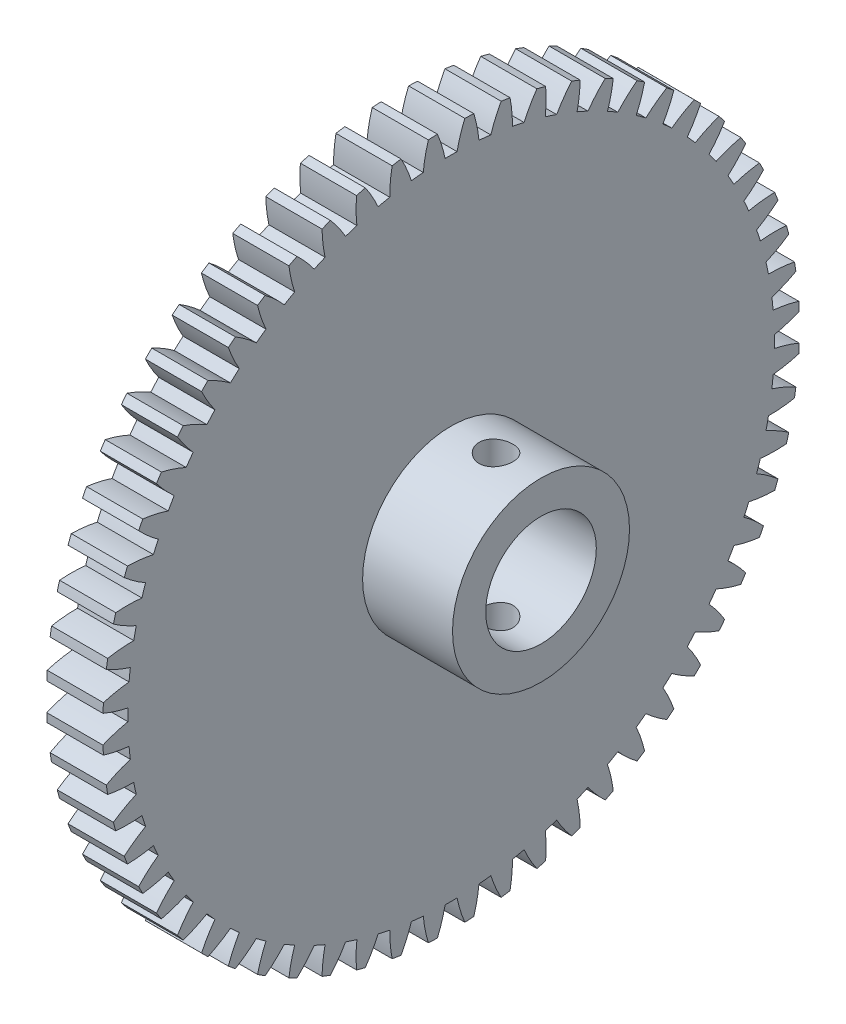
SolidWorks part; units mm, degrees
ref_plane "Plane1" through (0, 0, 0) normal (0, 0, 1) x (1, 0, 0)
ref_plane "Plane2" through (0, 0, 0) normal (0, 1, 0) x (1, 0, 0)
ref_plane "Plane3" through (0, 0, 0) normal (1, 0, 0) x (0, 0, -1)
sketch "HoldingSke" plane through (0, 0, 0) normal (0, 1, 0) x (1, 0, 0)
  line L0 (0, 0) -> (254, -439.9409)
  line L1 (-15, 0) -> (100, 0) construction
  line L2 (0, 0) -> (-2.1039, 2.3779)
  line L3 (0, 0) -> (-11.863, 4.5341)
  line L4 (0, 0) -> (4.318, 7.479)
  line L5 (0, 0) -> (-47.5972, -17.7524)
  line L6 (0, 0) -> (-5.2639, -3.5516)
  line L7 (-2.1039, 2.3779) -> (8.8308, 51.9871)
  line L8 (-76.2, 54.61) -> (-65.4837, 54.61)
  line L9 (-67.7845, 28.3722) -> (-49.3413, 33.142)
  line L10 (-76.2, 71.12) -> (104.1128, 71.12)
  line L11 (0, 0) -> (-6.35, 0)
  line L12 (-76.2, 101.6) -> (-76.1492, 101.6)
  line L13 (24.9733, 27.94) -> (52.9518, 28.4284)
  line L14 (24.9733, 27.94) -> (25.0241, 27.9398)
  line L15 (24.9733, 27.94) -> (100.4021, 29.52)
  circle A0 centre (0, 0) radius 4.7625
  circle A1 centre (0, 0) radius 36.5252
  circle A2 centre (0, 0) radius 38.1
  circle A3 centre (0, 0) radius 4.7625
  dimension "Num_teeth" = 60
  dimension "H" = 19.05
  dimension "Pitch_radius" = 180.3128
  dimension "Width" = 6.35
  dimension "Thickness" = 6.35
sketch "BasProSke" plane through (0, 0, 0) normal (0, 1, 0) x (1, 0, 0)
  line L0 (-10, 0) -> (60, 0) construction
  line L1 (0, 0) -> (0, 39.37)
  line L2 (0, 0) -> (6.35, 0)
  line L3 (6.35, 0) -> (6.35, 39.37)
  line L4 (6.35, 39.37) -> (0, 39.37)
  dimension "Thickness" = 6.35
  dimension "Diameter" = 78.74
revolve "Base-Revolve" add sketch "BasProSke" angle 360 about L0
sketch "TooCutSke" plane through (0, 0, 0) normal (1, 0, 0) x (0, 0, -1)
  line L1 (0, 0) -> (0, 107) construction
  line L2 (0, 0) -> (-1.0862, 38.0845) construction
  line L3 (0, 0) -> (-3.9869, 76.0739) construction
  line L4 (-1.0862, 38.0845) -> (-1.9934, 38.037) construction
  arc A0 (0.674, 36.519) -> (-0.674, 36.519) centre (0, 0) ccw
  arc A1 (1.5613, 39.3644) -> (-1.5613, 39.3644) centre (0, 0) ccw
  circle A2 centre (0, 0) radius 38.1 construction
  circle A3 centre (0, 0) radius 36.8864 construction
  arc A4 (-0.674, 36.519) -> (-1.5613, 39.3644) centre (-15.597, 33.4267) ccw
  arc A5 (1.5613, 39.3644) -> (0.674, 36.519) centre (15.597, 33.4267) ccw
extrude "ToothCut" cut sketch "TooCutSke" along normal through all
fillet "Breaks" [suppressed] radius 0.0254 tangent propagation no
fillet "RootFillets" [suppressed] radius 0.3048
pattern_circular "TeethCuts" count 60 every 6 about axis through (-10, 0, 0) along (1, 0, 0) of "ToothCut", "RootFillets", "Breaks"
sketch "HubNeaOneSke" plane through (0, 0, 0) normal (-1, 0, 0) x (0, 0, 1)
  circle A0 centre (0, 0) radius 36.5252
  dimension "Diameter" = 73.0504
extrude "HubNearOne" [suppressed] add sketch "HubNeaOneSke" along normal blind 44.4501
sketch "HubNeaBotSke" plane through (0, 0, 0) normal (-1, 0, 0) x (0, 0, 1)
  circle A0 centre (0, 0) radius 36.5252
  dimension "Diameter" = 73.0504
extrude "HubNearBoth" [suppressed] add sketch "HubNeaBotSke" along normal blind 22.225
ref_plane "FarPln" through (6.35, 0, 0) normal (1, 0, 0) x (0, 0, -1)
sketch "HubFarSke" plane through (6.35, 0, 0) normal (1, 0, 0) x (0, 0, -1)
  circle A0 centre (0, 0) radius 36.5252
  dimension "Diameter" = 73.0504
extrude "HubFar" [suppressed] add sketch "HubFarSke" along normal blind 22.225
sketch "BorSke" plane through (0, 0, 0) normal (1, 0, 0) x (0, 0, -1)
  circle A0 centre (0, 0) radius 6.25
  dimension "D1" = 12.5
extrude "Bore" cut sketch "BorSke" along normal mid plane 101.6001
sketch "KeySke" plane through (0, 0, 0) normal (1, 0, 0) x (0, 0, -1)
  line L0 (-1.1913, 0) -> (-1.1913, 5.9538)
  line L1 (-1.1913, 5.9538) -> (1.1913, 5.9538)
  line L2 (1.1913, 5.9538) -> (1.1913, 0)
  line L3 (0, 0) -> (0, 34) construction
  line L4 (-1.1913, 0) -> (1.1913, 0)
  dimension "Width" = 2.3825
extrude "Keyway" [suppressed] cut sketch "KeySke" along normal mid plane 101.6001
pattern_circular "Keyway2" [suppressed] count 2 every 90 about axis through (-10, 0, 0) along (1, 0, 0) reverse direction yes
sketch "Sketch1" plane through (6.35, 0, 0) normal (1, 0, 0) x (0, 0, -1)
  circle A0 centre (0, 0) radius 6.25 construction
  circle A1 centre (0, 0) radius 6.25
  circle A3 centre (0, 0) radius 10
  dimension "D1" = 20
extrude "Boss-Extrude1" add sketch "Sketch1" along normal blind 10.16
sketch "Sketch2" plane through (0, 0, 0) normal (0, 1, 0) x (1, 0, 0)
  circle A0 centre (11.43, 0) radius 1.905
  dimension "D1" = 3.81
extrude "Cut-Extrude1" cut sketch "Sketch2" against normal through all and the other way through all contours A0
equation "' \"Pitch@HoldingSke\" = 4"
equation "' \"Num_teeth@HoldingSke\" = 12"
equation "' \"Ap@HoldingSke\" =  20"
equation "' \"Ap@HoldingSke\" = 20"
equation "' \"Width@HoldingSke\" = 0.5"
equation "' \"Hub_dia@HoldingSke\"= 1"
equation "' \"Hub_dia@HoldingSke\" = 1"
equation "' \"Overall_len@HoldingSke\" = 1.0"
equation "' \"Bore@HoldingSke\" = 0.75"
equation "' \"T_dim@HoldingSke\" = 0.85"
equation "' \"Width@KeySke\" = 0.25"
equation "' \"Show_teeth@HoldingSke\" = 13"
equation "' \"Backlash@HoldingSke\" = 0.009"
equation "' \"Addendum_fac@HoldingSke\" = 1.0"
equation "' \"Dedendum_fac@HoldingSke\" = 1.25"
equation "' \"Dedendum_add@HoldingSke\" = 0.00005"
equation "' \"Clearance_fac@HoldingSke\" = 0.25"
equation "' \"Pitch@HoldingSke\" = 0.5"
equation "' \"Num_teeth@HoldingSke\" = 23"
equation "' \"Show_teeth@HoldingSke\" = 23"
equation "' \"Backlash@HoldingSke\" = 0.0375"
equation "\"Overcut_dia@TooCutSke\" = (\"Num_teeth@HoldingSke\" + 2 * \"Addendum_fac@HoldingSke\") / \"Pitch@HoldingSke\" + 0.002"
equation "\"Pitch_dia@TooCutSke\" = \"Num_teeth@HoldingSke\" / \"Pitch@HoldingSke\""
equation "\"Base_dia@TooCutSke\" = \"Num_teeth@HoldingSke\" / \"Pitch@HoldingSke\" * cos((\"Ap@HoldingSke\"  * 3.14159265 / 180))"
equation "\"Root_dia@TooCutSke\" = (\"Num_teeth@HoldingSke\" + 2) / \"Pitch@HoldingSke\" - 2 * (\"Addendum_fac@HoldingSke\" + \"Dedendum_fac@HoldingSke\") / \"Pitch@HoldingSke\" - \"Dedendum_add@HoldingSke\" * 2"
equation "\"Half_ang@TooCutSke\" = 180 / \"Num_teeth@HoldingSke\""
equation "\"Half_CT@TooCutSke\" = \"Num_teeth@HoldingSke\" / \"Pitch@HoldingSke\" * sin((3.14159265 / 2 / \"Num_teeth@HoldingSke\")) / 2 - 7 * \"Backlash@HoldingSke\" / 4"
equation "\"Flank_rad@TooCutSke\" = \"Num_teeth@HoldingSke\" / \"Pitch@HoldingSke\" / 5"
equation "\"Radius@RootFillets\" = \"Clearance_fac@HoldingSke\" / \"Pitch@HoldingSke\" + \"Dedendum_add@HoldingSke\""
equation "\"Break_rad@Breaks\" = 0.02 / \"Pitch@HoldingSke\""
equation "\"Thickness@HoldingSke\" = \"Width@HoldingSke\""
equation "\"OAL@HoldingSke\" = \"Thickness@HoldingSke\""
equation "\"MHD@HoldingSke\" = (\"Num_teeth@HoldingSke\" + 2) / \"Pitch@HoldingSke\" - 2 * (\"Addendum_fac@HoldingSke\" + \"Dedendum_fac@HoldingSke\")  / \"Pitch@HoldingSke\" - \"Dedendum_add@HoldingSke\" * 2"
equation "\"MBD@HoldingSke\" = (\"Num_teeth@HoldingSke\" + 2) / \"Pitch@HoldingSke\" - 2 * (\"Addendum_fac@HoldingSke\" + \"Dedendum_fac@HoldingSke\")  / \"Pitch@HoldingSke\" - \"Dedendum_add@HoldingSke\" * 2 - 0.002"
equation "\"MHD@HoldingSke\" = ((sgn( \"MHD@HoldingSke\" - \"Hub_dia@HoldingSke\" )-1)*( \"MHD@HoldingSke\" - \"Hub_dia@HoldingSke\" ))/-2+ \"Hub_dia@HoldingSke\""
equation "\"MBD@HoldingSke\" = ((sgn( \"MBD@HoldingSke\" - \"Bore@HoldingSke\" )-1)*( \"MBD@HoldingSke\" - \"Bore@HoldingSke\" ))/-2+ \"Bore@HoldingSke\""
equation "\"OAL@HoldingSke\" = ((sgn( \"OAL@HoldingSke\" - \"Overall_len@HoldingSke\" )+1)*( \"OAL@HoldingSke\" - \"Overall_len@HoldingSke\" ))/2 + \"Overall_len@HoldingSke\" + 0.000002"
equation "\"Num_teeth@TeethCuts\" = int( \"Show_teeth@HoldingSke\" ) + 1"
equation "\"Num_teeth@TeethCuts\" = ((sgn( \"Num_teeth@TeethCuts\" - \"Num_teeth@HoldingSke\" )-1)*( \"Num_teeth@TeethCuts\" - \"Num_teeth@HoldingSke\" ))/-2+ \"Num_teeth@HoldingSke\""
equation "\"Num_teeth@TeethCuts\" = ((sgn( \"Num_teeth@TeethCuts\" - 2.0)+1)*( \"Num_teeth@TeethCuts\" - 2.0))/2 +2.0"
equation "\"Angle@TeethCuts\" = 360.0 / \"Num_teeth@HoldingSke\""
equation "\"Diameter@BasProSke\" = (\"Num_teeth@HoldingSke\" + 2 * \"Addendum_fac@HoldingSke\") / \"Pitch@HoldingSke\""
equation "\"Thickness@BasProSke\"  = \"Thickness@HoldingSke\""
equation "' \"Fillet_rad@BasProSke\" =  \"Thickness@HoldingSke\" * 0.05"
equation "' \"Fillet_rad@BasProSke\" = \"Thickness@HoldingSke\" * 0.05"
equation "\"MHD@HoldingSke\" = ((sgn( \"MHD@HoldingSke\" - \"Root_dia@TooCutSke\" )-1)*( \"MHD@HoldingSke\" - \"Root_dia@TooCutSke\" ))/-2+ \"Root_dia@TooCutSke\""
equation "\"Diameter@HubNeaOneSke\" = \"MHD@HoldingSke\""
equation "\"Length@HubNearOne\" = \"OAL@HoldingSke\" - \"Thickness@BasProSke\""
equation "\"Diameter@HubNeaBotSke\" = \"MHD@HoldingSke\""
equation "\"Length@HubNearBoth\" = ( \"OAL@HoldingSke\" - \"Thickness@BasProSke\" ) / 2.0"
equation "\"Thickness@FarPln\" = \"Thickness@BasProSke\""
equation "\"Diameter@HubFarSke\" = \"MHD@HoldingSke\""
equation "\"Length@HubFar\" = ( \"OAL@HoldingSke\" - \"Thickness@BasProSke\" ) / 2.0"
equation "\"D1@Bore\" = \"OAL@HoldingSke\" * 2.0"
equation "\"D1@Keyway\" = \"OAL@HoldingSke\" * 2.0"
equation "\"Offset@KeySke\" = \"T_dim@HoldingSke\" - \"MBD@HoldingSke\" / 2.0"
